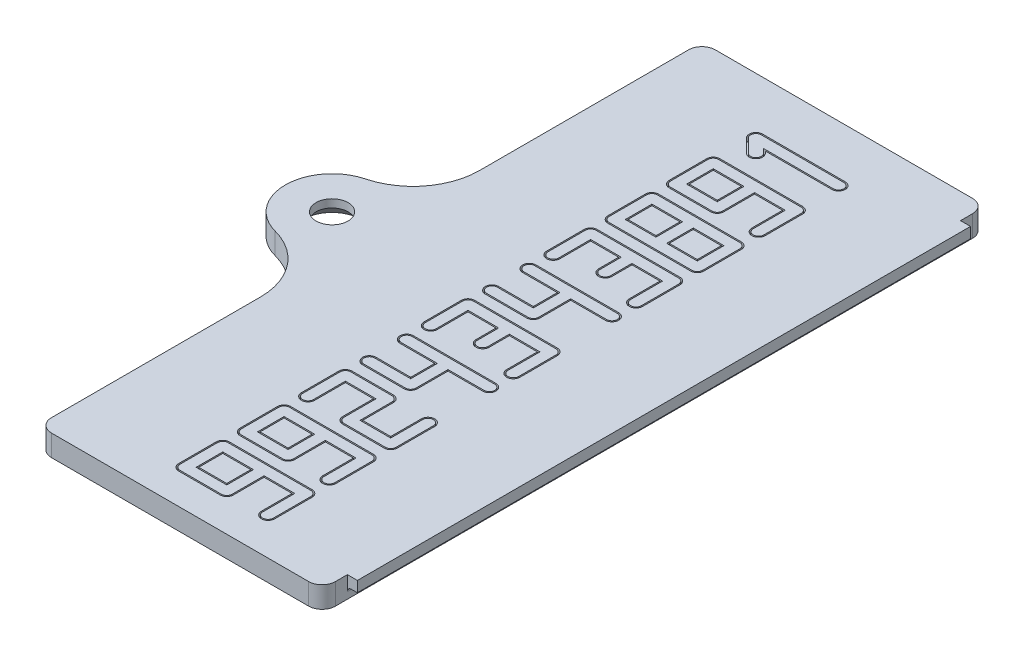
SolidWorks part; units mm, degrees
ref_plane "Front Plane" through (0, 0, 0) normal (0, 0, 1) x (1, 0, 0)
ref_plane "Top Plane" through (0, 0, 0) normal (0, 1, 0) x (1, 0, 0)
ref_plane "Right Plane" through (0, 0, 0) normal (1, 0, 0) x (0, 0, -1)
sketch "Door Plate 1.6 + screw ear (R5 / R3.5) Sketch" plane through (0, 0, 0) normal (0, 1, 0) x (1, 0, 0)
  line L0 (9.35, 15.1) -> (30.65, 15.1)
  line L1 (30.65, 15.1) -> (30.65, 64.9)
  line L2 (30.65, 64.9) -> (9.35, 64.9)
  line L3 (9.35, 64.9) -> (9.35, 48.2236)
  line L4 (9.35, 31.7764) -> (9.35, 15.1)
  arc A0 (9.35, 31.7764) -> (5.6147, 36.6138) centre (4.35, 31.7764) ccw
  arc A1 (5.6147, 36.6138) -> (5.6147, 43.3862) centre (6.5, 40) cw
  arc A2 (5.6147, 43.3862) -> (9.35, 48.2236) centre (4.35, 48.2236) ccw
extrude "Door Plate 1.6 + screw ear (R5 / R3.5)" add sketch "Door Plate 1.6 + screw ear (R5 / R3.5) Sketch" along normal blind 1.6
ref_plane "Hook Flange Plane y0.8" through (0, 0.8, 0) normal (0, 1, 0) x (1, 0, 0)
sketch "Hook Flange 0.75 x 0.8 (inner-face plane) Sketch" plane through (0, 0.8, 0) normal (0, 1, 0) x (1, 0, 0)
  line L0 (30.5, 17) -> (31.4, 17)
  line L1 (31.4, 17) -> (31.4, 63)
  line L2 (31.4, 63) -> (30.5, 63)
  line L3 (30.5, 63) -> (30.5, 17)
extrude "Hook Flange 0.75 x 0.8 (inner-face plane)" add sketch "Hook Flange 0.75 x 0.8 (inner-face plane) Sketch" along normal blind 0.8
sketch "Screw Hole 2.4 (free) Sketch" plane through (0, 0, 0) normal (0, 1, 0) x (1, 0, 0)
  circle A0 centre (6.5, 40) radius 1.2
extrude "Screw Hole 2.4 (free)" cut sketch "Screw Hole 2.4 (free) Sketch" along normal through all
chamfer "Screw CSK 90deg (M2)" distance 1 angle 45 1 edges at (6.5, 0, -38.8)
fillet "Door Corners R1 (print)" radius 1 4 edges at (9.35, 0.8, -64.9) (30.65, 0.8, -64.9) (30.65, 0.8, -15.1) (9.35, 0.8, -15.1)
fillet "Hook Flange Root Fillet R0.3" radius 0.3 1 edges at (30.65, 0.8, -40)
ref_plane "Number Plane y1.6" through (0, 1.6, 0) normal (0, 1, 0) x (1, 0, 0)
sketch "Phone Number 9924343891 Slits (0.8 stroke) Sketch" plane through (0, 1.6, 0) normal (0, 1, 0) x (1, 0, 0)
  line L0 (20.7, 17.4) -> (17.6, 17.4)
  line L1 (17.1, 17.9) -> (17.1, 20.7)
  line L2 (17.6, 21.2) -> (23.8, 21.2)
  line L3 (24.3, 20.7) -> (24.3, 17.9)
  line L4 (23.3, 17.9) -> (23.3, 20.2)
  line L5 (23.3, 20.2) -> (21.2, 20.2)
  line L6 (21.2, 20.2) -> (21.2, 17.9)
  line L7 (17.2, 20.7) -> (17.2, 17.9)
  line L8 (17.6, 17.5) -> (20.7, 17.5)
  line L9 (21.1, 17.9) -> (21.1, 20.3)
  line L10 (21.1, 20.3) -> (23.4, 20.3)
  line L11 (23.4, 20.3) -> (23.4, 17.9)
  line L12 (24.2, 17.9) -> (24.2, 20.7)
  line L13 (23.8, 21.1) -> (17.6, 21.1)
  line L14 (20.7, 22) -> (17.6, 22)
  line L15 (17.1, 22.5) -> (17.1, 25.3)
  line L16 (17.6, 25.8) -> (23.8, 25.8)
  line L17 (24.3, 25.3) -> (24.3, 22.5)
  line L18 (23.3, 22.5) -> (23.3, 24.8)
  line L19 (23.3, 24.8) -> (21.2, 24.8)
  line L20 (21.2, 24.8) -> (21.2, 22.5)
  line L21 (17.2, 25.3) -> (17.2, 22.5)
  line L22 (17.6, 22.1) -> (20.7, 22.1)
  line L23 (21.1, 22.5) -> (21.1, 24.9)
  line L24 (21.1, 24.9) -> (23.4, 24.9)
  line L25 (23.4, 24.9) -> (23.4, 22.5)
  line L26 (24.2, 22.5) -> (24.2, 25.3)
  line L27 (23.8, 25.7) -> (17.6, 25.7)
  line L28 (24.3, 29.9) -> (24.3, 27.1)
  line L29 (23.8, 26.6) -> (20.7, 26.6)
  line L30 (20.2, 27.1) -> (20.2, 29.4)
  line L31 (20.2, 29.4) -> (18.1, 29.4)
  line L32 (18.1, 29.4) -> (18.1, 27.1)
  line L33 (17.1, 27.1) -> (17.1, 29.9)
  line L34 (17.6, 30.4) -> (20.7, 30.4)
  line L35 (21.2, 29.9) -> (21.2, 27.6)
  line L36 (21.2, 27.6) -> (23.3, 27.6)
  line L37 (23.3, 27.6) -> (23.3, 29.9)
  line L38 (18, 29.5) -> (18, 27.1)
  line L39 (17.2, 27.1) -> (17.2, 29.9)
  line L40 (17.6, 30.3) -> (20.7, 30.3)
  line L41 (21.1, 29.9) -> (21.1, 27.5)
  line L42 (21.1, 27.5) -> (23.4, 27.5)
  line L43 (23.4, 27.5) -> (23.4, 29.9)
  line L44 (24.2, 29.9) -> (24.2, 27.1)
  line L45 (23.8, 26.7) -> (20.7, 26.7)
  line L46 (20.3, 27.1) -> (20.3, 29.5)
  line L47 (20.3, 29.5) -> (18, 29.5)
  line L48 (23.8, 34) -> (21.2, 34)
  line L49 (21.2, 34) -> (21.2, 31.7)
  line L50 (20.7, 31.2) -> (17.6, 31.2)
  line L51 (17.6, 32.2) -> (20.2, 32.2)
  line L52 (20.2, 32.2) -> (20.2, 34)
  line L53 (20.2, 34) -> (17.6, 34)
  line L54 (17.6, 35) -> (23.8, 35)
  line L55 (21.1, 31.7) -> (21.1, 34.1)
  line L56 (21.1, 34.1) -> (23.8, 34.1)
  line L57 (23.8, 34.9) -> (17.6, 34.9)
  line L58 (17.6, 34.1) -> (20.3, 34.1)
  line L59 (20.3, 34.1) -> (20.3, 32.1)
  line L60 (20.3, 32.1) -> (17.6, 32.1)
  line L61 (17.6, 31.3) -> (20.7, 31.3)
  line L62 (23.3, 36.3) -> (23.3, 38.6)
  line L63 (23.3, 38.6) -> (21.2, 38.6)
  line L64 (21.2, 38.6) -> (21.2, 37.1)
  line L65 (20.2, 37.1) -> (20.2, 38.6)
  line L66 (20.2, 38.6) -> (18.1, 38.6)
  line L67 (18.1, 38.6) -> (18.1, 36.3)
  line L68 (17.1, 36.3) -> (17.1, 39.1)
  line L69 (17.6, 39.6) -> (23.8, 39.6)
  line L70 (24.3, 39.1) -> (24.3, 36.3)
  line L71 (17.2, 36.3) -> (17.2, 39.1)
  line L72 (17.6, 39.5) -> (23.8, 39.5)
  line L73 (24.2, 39.1) -> (24.2, 36.3)
  line L74 (23.4, 36.3) -> (23.4, 38.7)
  line L75 (23.4, 38.7) -> (21.1, 38.7)
  line L76 (21.1, 38.7) -> (21.1, 37.1)
  line L77 (20.3, 37.1) -> (20.3, 38.7)
  line L78 (20.3, 38.7) -> (18, 38.7)
  line L79 (18, 38.7) -> (18, 36.3)
  line L80 (23.8, 43.2) -> (21.2, 43.2)
  line L81 (21.2, 43.2) -> (21.2, 40.9)
  line L82 (20.7, 40.4) -> (17.6, 40.4)
  line L83 (17.6, 41.4) -> (20.2, 41.4)
  line L84 (20.2, 41.4) -> (20.2, 43.2)
  line L85 (20.2, 43.2) -> (17.6, 43.2)
  line L86 (17.6, 44.2) -> (23.8, 44.2)
  line L87 (21.1, 40.9) -> (21.1, 43.3)
  line L88 (21.1, 43.3) -> (23.8, 43.3)
  line L89 (23.8, 44.1) -> (17.6, 44.1)
  line L90 (17.6, 43.3) -> (20.3, 43.3)
  line L91 (20.3, 43.3) -> (20.3, 41.3)
  line L92 (20.3, 41.3) -> (17.6, 41.3)
  line L93 (17.6, 40.5) -> (20.7, 40.5)
  line L94 (23.3, 45.5) -> (23.3, 47.8)
  line L95 (23.3, 47.8) -> (21.2, 47.8)
  line L96 (21.2, 47.8) -> (21.2, 46.3)
  line L97 (20.2, 46.3) -> (20.2, 47.8)
  line L98 (20.2, 47.8) -> (18.1, 47.8)
  line L99 (18.1, 47.8) -> (18.1, 45.5)
  line L100 (17.1, 45.5) -> (17.1, 48.3)
  line L101 (17.6, 48.8) -> (23.8, 48.8)
  line L102 (24.3, 48.3) -> (24.3, 45.5)
  line L103 (17.2, 45.5) -> (17.2, 48.3)
  line L104 (17.6, 48.7) -> (23.8, 48.7)
  line L105 (24.2, 48.3) -> (24.2, 45.5)
  line L106 (23.4, 45.5) -> (23.4, 47.9)
  line L107 (23.4, 47.9) -> (21.1, 47.9)
  line L108 (21.1, 47.9) -> (21.1, 46.3)
  line L109 (20.3, 46.3) -> (20.3, 47.9)
  line L110 (20.3, 47.9) -> (18, 47.9)
  line L111 (18, 47.9) -> (18, 45.5)
  line L112 (24.3, 52.9) -> (24.3, 50.1)
  line L113 (23.8, 49.6) -> (17.6, 49.6)
  line L114 (17.1, 50.1) -> (17.1, 52.9)
  line L115 (17.6, 53.4) -> (23.8, 53.4)
  line L116 (24.2, 50.1) -> (24.2, 52.9)
  line L117 (23.8, 53.3) -> (17.6, 53.3)
  line L118 (17.2, 52.9) -> (17.2, 50.1)
  line L119 (17.6, 49.7) -> (23.8, 49.7)
  line L120 (20.7, 54.2) -> (17.6, 54.2)
  line L121 (17.1, 54.7) -> (17.1, 57.5)
  line L122 (17.6, 58) -> (23.8, 58)
  line L123 (24.3, 57.5) -> (24.3, 54.7)
  line L124 (23.3, 54.7) -> (23.3, 57)
  line L125 (23.3, 57) -> (21.2, 57)
  line L126 (21.2, 57) -> (21.2, 54.7)
  line L127 (17.2, 57.5) -> (17.2, 54.7)
  line L128 (17.6, 54.3) -> (20.7, 54.3)
  line L129 (21.1, 54.7) -> (21.1, 57.1)
  line L130 (21.1, 57.1) -> (23.4, 57.1)
  line L131 (23.4, 57.1) -> (23.4, 54.7)
  line L132 (24.2, 54.7) -> (24.2, 57.5)
  line L133 (23.8, 57.9) -> (17.6, 57.9)
  line L134 (17.6, 61.2) -> (23.8, 61.2)
  line L135 (23.8, 60.2) -> (18.8071, 60.2)
  line L136 (18.8071, 60.2) -> (18.9536, 60.0536)
  line L137 (18.2464, 59.3464) -> (17.2464, 60.3464)
  line L138 (18.5657, 60.3) -> (18.8828, 59.9828)
  line L139 (18.3172, 59.4172) -> (17.3172, 60.4172)
  line L140 (17.6, 61.1) -> (23.8, 61.1)
  line L141 (23.8, 60.3) -> (18.5657, 60.3)
  arc A0 (21.2, 17.9) -> (20.7, 17.4) centre (20.7, 17.9) cw
  arc A1 (17.6, 17.4) -> (17.1, 17.9) centre (17.6, 17.9) cw
  arc A2 (17.1, 20.7) -> (17.6, 21.2) centre (17.6, 20.7) cw
  arc A3 (23.8, 21.2) -> (24.3, 20.7) centre (23.8, 20.7) cw
  arc A4 (24.3, 17.9) -> (23.3, 17.9) centre (23.8, 17.9) cw
  arc A5 (17.6, 21.1) -> (17.2, 20.7) centre (17.6, 20.7) ccw
  arc A6 (17.2, 17.9) -> (17.6, 17.5) centre (17.6, 17.9) ccw
  arc A7 (20.7, 17.5) -> (21.1, 17.9) centre (20.7, 17.9) ccw
  arc A8 (23.4, 17.9) -> (24.2, 17.9) centre (23.8, 17.9) ccw
  arc A9 (24.2, 20.7) -> (23.8, 21.1) centre (23.8, 20.7) ccw
  arc A10 (21.2, 22.5) -> (20.7, 22) centre (20.7, 22.5) cw
  arc A11 (17.6, 22) -> (17.1, 22.5) centre (17.6, 22.5) cw
  arc A12 (17.1, 25.3) -> (17.6, 25.8) centre (17.6, 25.3) cw
  arc A13 (23.8, 25.8) -> (24.3, 25.3) centre (23.8, 25.3) cw
  arc A14 (24.3, 22.5) -> (23.3, 22.5) centre (23.8, 22.5) cw
  arc A15 (17.6, 25.7) -> (17.2, 25.3) centre (17.6, 25.3) ccw
  arc A16 (17.2, 22.5) -> (17.6, 22.1) centre (17.6, 22.5) ccw
  arc A17 (20.7, 22.1) -> (21.1, 22.5) centre (20.7, 22.5) ccw
  arc A18 (23.4, 22.5) -> (24.2, 22.5) centre (23.8, 22.5) ccw
  arc A19 (24.2, 25.3) -> (23.8, 25.7) centre (23.8, 25.3) ccw
  arc A20 (23.3, 29.9) -> (24.3, 29.9) centre (23.8, 29.9) cw
  arc A21 (24.3, 27.1) -> (23.8, 26.6) centre (23.8, 27.1) cw
  arc A22 (20.7, 26.6) -> (20.2, 27.1) centre (20.7, 27.1) cw
  arc A23 (18.1, 27.1) -> (17.1, 27.1) centre (17.6, 27.1) cw
  arc A24 (17.1, 29.9) -> (17.6, 30.4) centre (17.6, 29.9) cw
  arc A25 (20.7, 30.4) -> (21.2, 29.9) centre (20.7, 29.9) cw
  arc A26 (18, 27.1) -> (17.2, 27.1) centre (17.6, 27.1) cw
  arc A27 (17.2, 29.9) -> (17.6, 30.3) centre (17.6, 29.9) cw
  arc A28 (20.7, 30.3) -> (21.1, 29.9) centre (20.7, 29.9) cw
  arc A29 (23.4, 29.9) -> (24.2, 29.9) centre (23.8, 29.9) cw
  arc A30 (24.2, 27.1) -> (23.8, 26.7) centre (23.8, 27.1) cw
  arc A31 (20.7, 26.7) -> (20.3, 27.1) centre (20.7, 27.1) cw
  arc A32 (23.8, 35) -> (24.3, 34.5) centre (23.8, 34.5) cw
  arc A33 (24.3, 34.5) -> (23.8, 34) centre (23.8, 34.5) cw
  arc A34 (21.2, 31.7) -> (20.7, 31.2) centre (20.7, 31.7) cw
  arc A35 (17.6, 31.2) -> (17.6, 32.2) centre (17.6, 31.7) cw
  arc A36 (17.6, 34) -> (17.6, 35) centre (17.6, 34.5) cw
  arc A37 (20.7, 31.3) -> (21.1, 31.7) centre (20.7, 31.7) ccw
  arc A38 (23.8, 34.1) -> (24.2, 34.5) centre (23.8, 34.5) ccw
  arc A39 (24.2, 34.5) -> (23.8, 34.9) centre (23.8, 34.5) ccw
  arc A40 (17.6, 34.9) -> (17.6, 34.1) centre (17.6, 34.5) ccw
  arc A41 (17.6, 32.1) -> (17.6, 31.3) centre (17.6, 31.7) ccw
  arc A42 (21.2, 37.1) -> (20.2, 37.1) centre (20.7, 37.1) cw
  arc A43 (18.1, 36.3) -> (17.1, 36.3) centre (17.6, 36.3) cw
  arc A44 (17.1, 39.1) -> (17.6, 39.6) centre (17.6, 39.1) cw
  arc A45 (23.8, 39.6) -> (24.3, 39.1) centre (23.8, 39.1) cw
  arc A46 (24.3, 36.3) -> (23.3, 36.3) centre (23.8, 36.3) cw
  arc A47 (18, 36.3) -> (17.2, 36.3) centre (17.6, 36.3) cw
  arc A48 (17.2, 39.1) -> (17.6, 39.5) centre (17.6, 39.1) cw
  arc A49 (23.8, 39.5) -> (24.2, 39.1) centre (23.8, 39.1) cw
  arc A50 (24.2, 36.3) -> (23.4, 36.3) centre (23.8, 36.3) cw
  arc A51 (21.1, 37.1) -> (20.3, 37.1) centre (20.7, 37.1) cw
  arc A52 (23.8, 44.2) -> (24.3, 43.7) centre (23.8, 43.7) cw
  arc A53 (24.3, 43.7) -> (23.8, 43.2) centre (23.8, 43.7) cw
  arc A54 (21.2, 40.9) -> (20.7, 40.4) centre (20.7, 40.9) cw
  arc A55 (17.6, 40.4) -> (17.6, 41.4) centre (17.6, 40.9) cw
  arc A56 (17.6, 43.2) -> (17.6, 44.2) centre (17.6, 43.7) cw
  arc A57 (20.7, 40.5) -> (21.1, 40.9) centre (20.7, 40.9) ccw
  arc A58 (23.8, 43.3) -> (24.2, 43.7) centre (23.8, 43.7) ccw
  arc A59 (24.2, 43.7) -> (23.8, 44.1) centre (23.8, 43.7) ccw
  arc A60 (17.6, 44.1) -> (17.6, 43.3) centre (17.6, 43.7) ccw
  arc A61 (17.6, 41.3) -> (17.6, 40.5) centre (17.6, 40.9) ccw
  arc A62 (21.2, 46.3) -> (20.2, 46.3) centre (20.7, 46.3) cw
  arc A63 (18.1, 45.5) -> (17.1, 45.5) centre (17.6, 45.5) cw
  arc A64 (17.1, 48.3) -> (17.6, 48.8) centre (17.6, 48.3) cw
  arc A65 (23.8, 48.8) -> (24.3, 48.3) centre (23.8, 48.3) cw
  arc A66 (24.3, 45.5) -> (23.3, 45.5) centre (23.8, 45.5) cw
  arc A67 (18, 45.5) -> (17.2, 45.5) centre (17.6, 45.5) cw
  arc A68 (17.2, 48.3) -> (17.6, 48.7) centre (17.6, 48.3) cw
  arc A69 (23.8, 48.7) -> (24.2, 48.3) centre (23.8, 48.3) cw
  arc A70 (24.2, 45.5) -> (23.4, 45.5) centre (23.8, 45.5) cw
  arc A71 (21.1, 46.3) -> (20.3, 46.3) centre (20.7, 46.3) cw
  arc A72 (23.8, 53.4) -> (24.3, 52.9) centre (23.8, 52.9) cw
  arc A73 (24.3, 50.1) -> (23.8, 49.6) centre (23.8, 50.1) cw
  arc A74 (17.6, 49.6) -> (17.1, 50.1) centre (17.6, 50.1) cw
  arc A75 (17.1, 52.9) -> (17.6, 53.4) centre (17.6, 52.9) cw
  arc A76 (23.8, 49.7) -> (24.2, 50.1) centre (23.8, 50.1) ccw
  arc A77 (24.2, 52.9) -> (23.8, 53.3) centre (23.8, 52.9) ccw
  arc A78 (17.6, 53.3) -> (17.2, 52.9) centre (17.6, 52.9) ccw
  arc A79 (17.2, 50.1) -> (17.6, 49.7) centre (17.6, 50.1) ccw
  arc A80 (21.2, 54.7) -> (20.7, 54.2) centre (20.7, 54.7) cw
  arc A81 (17.6, 54.2) -> (17.1, 54.7) centre (17.6, 54.7) cw
  arc A82 (17.1, 57.5) -> (17.6, 58) centre (17.6, 57.5) cw
  arc A83 (23.8, 58) -> (24.3, 57.5) centre (23.8, 57.5) cw
  arc A84 (24.3, 54.7) -> (23.3, 54.7) centre (23.8, 54.7) cw
  arc A85 (17.6, 57.9) -> (17.2, 57.5) centre (17.6, 57.5) ccw
  arc A86 (17.2, 54.7) -> (17.6, 54.3) centre (17.6, 54.7) ccw
  arc A87 (20.7, 54.3) -> (21.1, 54.7) centre (20.7, 54.7) ccw
  arc A88 (23.4, 54.7) -> (24.2, 54.7) centre (23.8, 54.7) ccw
  arc A89 (24.2, 57.5) -> (23.8, 57.9) centre (23.8, 57.5) ccw
  arc A90 (23.8, 61.2) -> (24.3, 60.7) centre (23.8, 60.7) cw
  arc A91 (24.3, 60.7) -> (23.8, 60.2) centre (23.8, 60.7) cw
  arc A92 (18.9536, 60.0536) -> (19.1, 59.7) centre (18.6, 59.7) cw
  arc A93 (19.1, 59.7) -> (18.2464, 59.3464) centre (18.6, 59.7) cw
  arc A94 (17.2464, 60.3464) -> (17.6, 61.2) centre (17.6, 60.7) cw
  arc A95 (18.8828, 59.9828) -> (19, 59.7) centre (18.6, 59.7) cw
  arc A96 (19, 59.7) -> (18.3172, 59.4172) centre (18.6, 59.7) cw
  arc A97 (17.3172, 60.4172) -> (17.6, 61.1) centre (17.6, 60.7) cw
  arc A98 (23.8, 61.1) -> (24.2, 60.7) centre (23.8, 60.7) cw
  arc A99 (24.2, 60.7) -> (23.8, 60.3) centre (23.8, 60.7) cw
extrude "Phone Number 9924343891 Slits (0.8 stroke)" cut sketch "Phone Number 9924343891 Slits (0.8 stroke) Sketch" against normal blind 0.4
sketch "Phone Number Counter Slits Sketch" plane through (0, 1.6, 0) normal (0, 1, 0) x (1, 0, 0)
  line L0 (18, 20.3) -> (18, 18.3)
  line L1 (18, 18.3) -> (20.3, 18.3)
  line L2 (20.3, 18.3) -> (20.3, 20.3)
  line L3 (20.3, 20.3) -> (18, 20.3)
  line L4 (20.2, 18.4) -> (20.2, 20.2)
  line L5 (20.2, 20.2) -> (18.1, 20.2)
  line L6 (18.1, 20.2) -> (18.1, 18.4)
  line L7 (18.1, 18.4) -> (20.2, 18.4)
  line L8 (18, 24.9) -> (18, 22.9)
  line L9 (18, 22.9) -> (20.3, 22.9)
  line L10 (20.3, 22.9) -> (20.3, 24.9)
  line L11 (20.3, 24.9) -> (18, 24.9)
  line L12 (20.2, 23) -> (20.2, 24.8)
  line L13 (20.2, 24.8) -> (18.1, 24.8)
  line L14 (18.1, 24.8) -> (18.1, 23)
  line L15 (18.1, 23) -> (20.2, 23)
  line L16 (23.4, 50.5) -> (23.4, 52.5)
  line L17 (23.4, 52.5) -> (21.1, 52.5)
  line L18 (21.1, 52.5) -> (21.1, 50.5)
  line L19 (21.1, 50.5) -> (23.4, 50.5)
  line L20 (21.2, 52.4) -> (21.2, 50.6)
  line L21 (21.2, 50.6) -> (23.3, 50.6)
  line L22 (23.3, 50.6) -> (23.3, 52.4)
  line L23 (23.3, 52.4) -> (21.2, 52.4)
  line L24 (20.3, 50.5) -> (20.3, 52.5)
  line L25 (20.3, 52.5) -> (18, 52.5)
  line L26 (18, 52.5) -> (18, 50.5)
  line L27 (18, 50.5) -> (20.3, 50.5)
  line L28 (18.1, 52.4) -> (18.1, 50.6)
  line L29 (18.1, 50.6) -> (20.2, 50.6)
  line L30 (20.2, 50.6) -> (20.2, 52.4)
  line L31 (20.2, 52.4) -> (18.1, 52.4)
  line L32 (18, 57.1) -> (18, 55.1)
  line L33 (18, 55.1) -> (20.3, 55.1)
  line L34 (20.3, 55.1) -> (20.3, 57.1)
  line L35 (20.3, 57.1) -> (18, 57.1)
  line L36 (20.2, 55.2) -> (20.2, 57)
  line L37 (20.2, 57) -> (18.1, 57)
  line L38 (18.1, 57) -> (18.1, 55.2)
  line L39 (18.1, 55.2) -> (20.2, 55.2)
extrude "Phone Number Counter Slits" cut sketch "Phone Number Counter Slits Sketch" against normal blind 0.4
